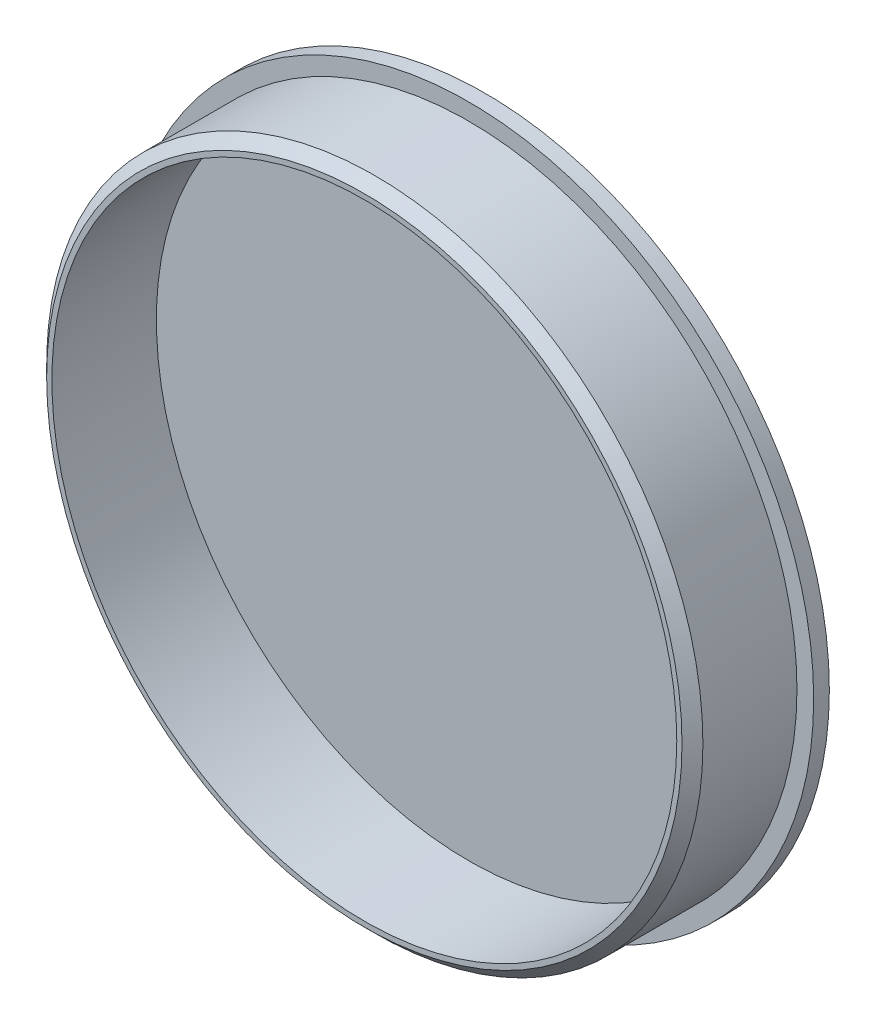
SolidWorks part; units mm, degrees
ref_plane "Front Plane" through (0, 0, 0) normal (0, 0, 1) x (1, 0, 0)
ref_plane "Top Plane" through (0, 0, 0) normal (0, 1, 0) x (1, 0, 0)
ref_plane "Right Plane" through (0, 0, 0) normal (1, 0, 0) x (0, 0, -1)
sketch "Sketch1" plane through (0, 0, 0) normal (0, 0, 1) x (1, 0, 0)
  circle A0 centre (0, 0) radius 33
  dimension "D1" = 66
extrude "Boss-Extrude1" add sketch "Sketch1" against normal mid plane 93.5
sketch "Sketch10" plane through (0, 0, 0) normal (1, 0, 0) x (0, 0, -1)
  line L0 (-64.25, 0) -> (-64.25, 15)
  line L1 (-46.75, 33) -> (-64.25, 15)
  line L2 (-1000, 0) -> (49000, 0) construction
  line L3 (-64.25, 0) -> (-46.75, 0)
  line L4 (-46.75, 0) -> (-46.75, 33)
  line L5 (46.75, -33) -> (46.75, 33) construction
  point P3 (-64.25, 0)
  dimension "D1" = 15
  dimension "D2" = 111
revolve "Revolve1" add sketch "Sketch10" angle 360 about L2
ref_plane "Plane1" through (0, 33, 0) normal (0, 1, 0) x (1, 0, 0)
sketch "Sketch11" plane through (-33, 33, 0) normal (0, -1, 0) x (0, 0, -1)
  line L0 (-64.25, 33) -> (46.75, 33) construction
  line L2 (-64.25, 48) -> (-64.25, 18) construction
  line L3 (46.75, 0) -> (46.75, 66) construction
  circle A0 centre (-44.25, 33) radius 2.1
  dimension "D1" = 4.2
  dimension "D2" = 91
extrude "Cut-Extrude1" cut sketch "Sketch11" along normal blind 10 and the other way through all
pattern_circular "CirPattern1" count 4 over 360 of bodies 112
sketch "Sketch12" plane through (0, 0, 64.25) normal (0, 0, 1) x (1, 0, 0)
  circle A0 centre (0, 0) radius 5
  dimension "D1" = 10
extrude "Boss-Extrude5" add sketch "Sketch12" along normal blind 54
sketch "Sketch13" plane through (0, 0, 0) normal (1, 0, 0) x (0, 0, -1)
  line L0 (-118.25, 5) -> (-118.25, -5) construction
  circle A0 centre (-79.25, 0) radius 1.5
  dimension "D1" = 3
  dimension "D2" = 39
extrude "Cut-Extrude2" cut sketch "Sketch13" against normal through all both and the other way through all
sketch "Sketch14" plane through (0, 0, 0) normal (1, 0, 0) x (0, 0, -1)
  line L0 (-64.25, 5) -> (-118.25, 5) construction
  line L1 (-118.25, 5) -> (-118.25, -5) construction
  circle A0 centre (-111.25, 5) radius 0.75
  dimension "D1" = 1.5
  dimension "D2" = 7
revolve "Cut-Revolve1" cut sketch "Sketch14" angle 360
sketch "Sketch15" plane through (0, 0, -46.75) normal (0, 0, -1) x (-1, 0, 0)
  circle A0 centre (0, 0) radius 46.534
extrude "Cut-Extrude5" [suppressed] cut sketch "Sketch15" along normal blind 10 from offset 3 offset against normal yes
shell "Shell1" [suppressed] thickness 1.5
sketch "Sketch16" [suppressed] plane through (0, 0, 0) normal (0, 1, 0) x (1, 0, 0)
  line L5 (21.5, -41.7863) -> (21.5, -40.65)
  line L6 (21.5, -40.65) -> (21.5, -47.85) construction
  line L7 (21.5, -40.65) -> (32.0238, -30.1262)
  line L8 (32.0238, -30.1262) -> (32.0238, -41.7863)
  line L9 (32.0238, -41.7863) -> (21.5, -41.7863)
  line L10 (31.5, -40.65) -> (21.5, -40.65) construction
  dimension "D1" = 45
extrude "Boss-Extrude7" [suppressed] add sketch "Sketch16" along normal mid plane 1.5
pattern_circular "CirPattern2" [suppressed] count 4 over 360 of bodies 120
sketch "Sketch17" [suppressed] plane through (0, 0, 62.75) normal (0, 0, -1) x (-1, 0, 0)
  circle A0 centre (0, 0) radius 3.5
extrude "Boss-Extrude9" [suppressed] add sketch "Sketch17" against normal blind 1.5
chamfer "Chamfer1" [suppressed] distance 0.5 angle 45
sketch "Sketch18" plane through (0, 0, -46.75) normal (0, 0, -1) x (-1, 0, 0)
  circle A0 centre (0, 0) radius 51.9919
extrude "Cut-Extrude6" cut sketch "Sketch18" against normal through all from offset 1.5 offset against normal yes
sketch "Sketch19" plane through (0, 0, -45.25) normal (0, 0, 1) x (1, 0, 0)
  circle A0 centre (0, 0) radius 31.4
  circle A1 centre (0, 0) radius 33 construction
  dimension "D1" = 1.6
extrude "Boss-Extrude10" add sketch "Sketch19" along normal blind 10
shell "Shell2" thickness 1.5 removed face at (31.4, 0, -35.25)
chamfer "Chamfer2" distance 1 angle 45 1 edges at (31.4, 0, -35.25)
